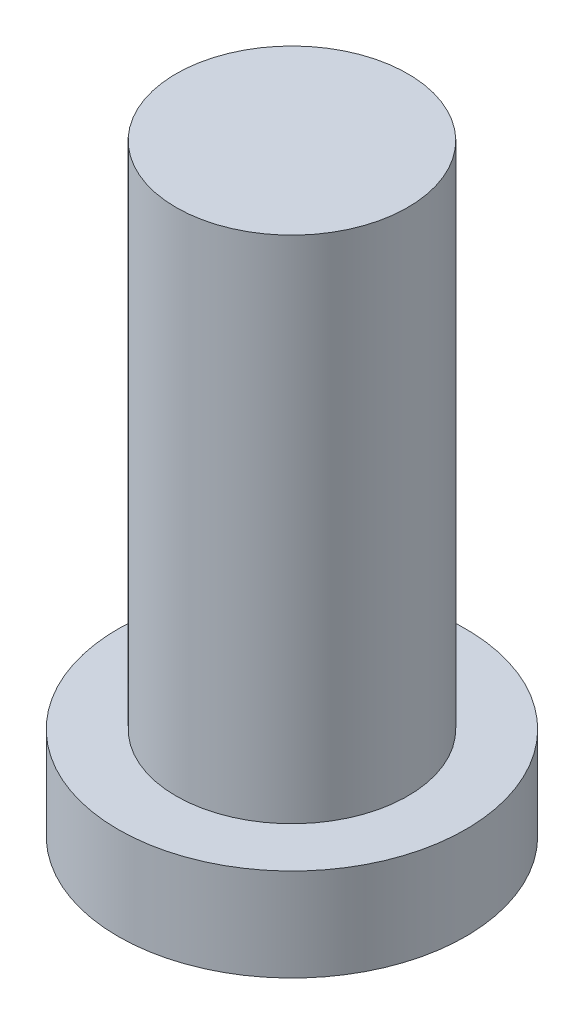
SolidWorks part; units mm, degrees
ref_plane "Front Plane" through (0, 0, 0) normal (0, 0, 1) x (1, 0, 0)
ref_plane "Top Plane" through (0, 0, 0) normal (0, 1, 0) x (1, 0, 0)
ref_plane "Right Plane" through (0, 0, 0) normal (1, 0, 0) x (0, 0, -1)
sketch "Sketch1" plane through (0, 0, 0) normal (0, 1, 0) x (1, 0, 0)
  circle A0 centre (0, 0) radius 7.5
  dimension "D1" = 15
extrude "Boss-Extrude3" add sketch "Sketch1" along normal blind 4
sketch "Sketch4" plane through (0, 4, 0) normal (0, 1, 0) x (1, 0, 0)
  circle A0 centre (0, 0) radius 5
  dimension "D1" = 10
extrude "Boss-Extrude4" add sketch "Sketch4" along normal blind 22
